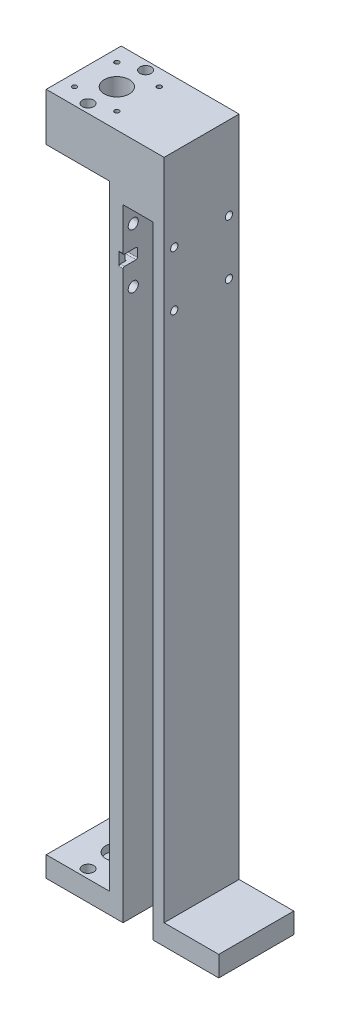
SolidWorks part; units mm, degrees
ref_plane "Front Plane" through (0, 0, 0) normal (0, 0, 1) x (1, 0, 0)
ref_plane "Top Plane" through (0, 0, 0) normal (0, 1, 0) x (1, 0, 0)
ref_plane "Right Plane" through (0, 0, 0) normal (1, 0, 0) x (0, 0, -1)
sketch "Sketch1" plane through (0, 0, 0) normal (0, 1, 0) x (1, 0, 0)
  line L5 (-28.12, -27.45) -> (-28.12, 27.45)
  line L6 (-28.12, -27.45) -> (28.12, -27.45)
  line L12 (28.12, 27.45) -> (28.12, -27.45)
  line L13 (28.12, 27.45) -> (-28.12, 27.45)
  circle A2 centre (-3.905, 21.045) radius 4.15
  circle A3 centre (-3.905, -21.045) radius 4.15
  point P5 (0, 27.45)
  point P6 (0, -27.45)
  point P15 (-28.12, 0)
  point P16 (28.12, 0)
  dimension "D1" = 42.09
  dimension "D2" = 8.3
  dimension "D3" = 8.3
  dimension "D8" = 24.215
  dimension "D4" = 6.405
  dimension "D5" = 56.24
  dimension "D6" = 54.9
  dimension "D7" = 6.405
extrude "Boss-Extrude1" add sketch "Sketch1" along normal blind 500 contours L13 L5 L6 A3 A2 region at (0.1418, 0, 0)
sketch "Sketch3" plane through (-28.12, 0, 0) normal (-1, 0, 0) x (0, 0, 1)
  line L2 (-27.45, 500) -> (-27.45, 0) construction
  line L9 (27.45, 500) -> (27.45, 0) construction
  line L11 (27.45, 465) -> (-27.45, 465)
  line L12 (27.45, 465) -> (27.45, 15)
  line L13 (27.45, 15) -> (-27.45, 15)
  line L14 (-27.45, 465) -> (-27.45, 15)
  point P0 (0, 15)
  point P2 (0, 465)
  dimension "D1" = 450
  dimension "D2" = 15
extrude "Cut-Extrude1" cut sketch "Sketch3" against normal blind 46.24
sketch "Sketch6" plane through (0, 500, 0) normal (0, 1, 0) x (1, 0, 0)
  line L0 (-3.905, 21.045) -> (-3.905, -21.045) construction
  line L1 (-28.12, -27.45) -> (-28.12, 27.45) construction
  line L3 (28.12, 27.45) -> (-28.12, 27.45) construction
  circle A0 centre (-3.905, 0) radius 9.15
  circle A1 centre (-19.405, 15.5) radius 1.65
  circle A2 centre (11.595, 15.5) radius 1.65
  circle A3 centre (11.595, -15.5) radius 1.65
  circle A4 centre (-19.405, -15.5) radius 1.65
  point P4 (-3.905, 0)
  dimension "D1" = 3.3
  dimension "D3" = 31
  dimension "D4" = 8.715
  dimension "D5" = 18.3
  dimension "D6" = 11.95
  dimension "D9" = 31
extrude "Cut-Extrude2" cut sketch "Sketch6" against normal blind 46.24
sketch "Sketch8" plane through (0, 15, 0) normal (0, 1, 0) x (1, 0, 0)
  circle A0 centre (-3.905, 0) radius 8.15
  circle A1 centre (-3.905, 0) radius 4.15
  dimension "D1" = 16.3
  dimension "D2" = 8.3
extrude "Cut-Extrude4" cut sketch "Sketch8" against normal blind 40 contours A1 region at (-3.905, 15, 0)
extrude "Cut-Extrude5" cut sketch "Sketch8<6>" against normal blind 5.2
sketch "Sketch8<6>" plane through (0, 15, 0) normal (0, 1, 0) x (1, 0, 0) same geometry as "Sketch8"
sketch "Sketch10" plane through (28.12, 0, 0) normal (1, 0, 0) x (0, 0, -1)
  line L0 (-27.45, 500) -> (-27.45, 0) construction
  line L1 (27.45, 500) -> (-27.45, 500)
  line L2 (27.45, 500) -> (27.45, 455)
  line L3 (27.45, 455) -> (-27.45, 455)
  line L4 (-27.45, 500) -> (-27.45, 455)
  dimension "D1" = 45
extrude "Boss-Extrude2" add sketch "Sketch10" along normal blind 22
sketch "Sketch11" plane through (0, 500, 0) normal (0, 1, 0) x (1, 0, 0)
  line L1 (50.12, 27.45) -> (58.12, 27.45)
  line L2 (50.12, 27.45) -> (50.12, -27.45)
  line L3 (50.12, -27.45) -> (58.12, -27.45)
  line L4 (58.12, 27.45) -> (58.12, -27.45)
  dimension "D1" = 8
  dimension "D2" = 54.9
extrude "Boss-Extrude3" add sketch "Sketch11" against normal blind 500
sketch "Sketch12" plane through (18.12, 0, 0) normal (-1, 0, 0) x (0, 0, 1)
  line L0 (-27.45, 465) -> (-27.45, 15) construction
  line L1 (27.45, 465) -> (-27.45, 465) construction
  circle A0 centre (-20, 439.3) radius 3.7
  circle A1 centre (-20, 439.3) radius 6
  circle A2 centre (20, 439.3) radius 6
  circle A3 centre (20, 439.3) radius 3.7
  circle A4 centre (20, 399.3) radius 6
  circle A5 centre (20, 399.3) radius 3.7
  circle A6 centre (-20, 399.3) radius 6
  circle A7 centre (-20, 399.3) radius 3.7
  dimension "D3" = 7.4
  dimension "D4" = 12
  dimension "D5" = 2
  dimension "D1" = 7.45
  dimension "D2" = 25.7
  dimension "D7" = 40
  dimension "D8" = 40
  dimension "D6" = 2
extrude "Cut-Extrude7" cut sketch "Sketch12" against normal blind 20 contours A7 | A0 | A5 | A3 region at (18.12, 439.3, -20) region at (18.12, 439.3, 20) region at (18.12, 399.3, 20) region at (18.12, 399.3, -20)
extrude "Cut-Extrude8" cut sketch "Sketch12<4>" against normal blind 4.8
sketch "Sketch12<4>" plane through (18.12, 0, 0) normal (-1, 0, 0) x (0, 0, 1) same geometry as "Sketch12"
sketch "Sketch13" plane through (58.12, 0, 0) normal (1, 0, 0) x (0, 0, -1)
  line L0 (27.45, 0) -> (27.45, 500) construction
  line L1 (-27.45, 0) -> (27.45, 0)
  line L2 (-27.45, 0) -> (-27.45, 15)
  line L3 (-27.45, 15) -> (27.45, 15)
  line L4 (27.45, 0) -> (27.45, 15)
  dimension "D1" = 15
extrude "Boss-Extrude4" add sketch "Sketch13" along normal blind 40
sketch "Sketch14" plane through (0, 465, 0) normal (0, -1, 0) x (1, 0, 0)
  circle A0 centre (-19.405, 15.5) radius 5
  circle A1 centre (11.595, 15.5) radius 5
  circle A2 centre (11.595, -15.5269) radius 5
  circle A3 centre (-19.405, -15.5269) radius 5
  dimension "D1" = 10
  dimension "D4" = 31
  dimension "D5" = 31.0269
  dimension "D2" = 2
  dimension "D3" = 2
extrude "Cut-Extrude9" cut sketch "Sketch14" against normal blind 25
sketch "Sketch15" plane through (50.12, 0, 0) normal (-1, 0, 0) x (0, 0, 1)
  circle A0 centre (-20, 439.3) radius 2.65
  circle A1 centre (20, 439.3) radius 2.65
  circle A2 centre (20, 399.3) radius 2.65
  circle A3 centre (-20, 399.3) radius 2.65
  dimension "D1" = 5.3
  dimension "D4" = 40
  dimension "D5" = 40
  dimension "D2" = 2
  dimension "D3" = 2
extrude "Cut-Extrude10" cut sketch "Sketch15" against normal blind 24.5
sketch "Sketch16" plane through (18.12, 0, 0) normal (-1, 0, 0) x (0, 0, 1)
  line L0 (-20, 439.3) -> (20, 439.3)
  line L1 (0, 439.3) -> (0, 396.651) construction
  line L2 (23, 416.4) -> (23, 422.2)
  line L7 (-22, 415.4) -> (-18, 415.4)
  line L8 (-23, 416.4) -> (-23, 422.2)
  line L9 (-22, 423.2) -> (-18, 423.2)
  line L10 (-17, 416.4) -> (-17, 422.2)
  line L11 (22, 415.4) -> (18, 415.4)
  line L12 (17, 416.4) -> (17, 422.2)
  line L13 (22, 423.2) -> (18, 423.2)
  arc A0 (-18, 415.4) -> (-17, 416.4) centre (-18, 416.4) ccw
  arc A1 (-22, 415.4) -> (-23, 416.4) centre (-22, 416.4) cw
  arc A2 (-17, 422.2) -> (-18, 423.2) centre (-18, 422.2) ccw
  arc A3 (-22, 423.2) -> (-23, 422.2) centre (-22, 422.2) ccw
  circle A4 centre (-20, 399.3) radius 6 construction
  arc A5 (22, 423.2) -> (23, 422.2) centre (22, 422.2) cw
  arc A6 (22, 415.4) -> (23, 416.4) centre (22, 416.4) ccw
  circle A7 centre (-20, 439.3) radius 6 construction
  arc A8 (18, 415.4) -> (17, 416.4) centre (18, 416.4) cw
  arc A9 (17, 422.2) -> (18, 423.2) centre (18, 422.2) cw
  point P36 (-20, 423.2)
  dimension "D1" = 1
  dimension "D3" = 5.8
  dimension "D2" = 16.1
  dimension "D4" = 4
  dimension "D5" = 16.1
extrude "Cut-Extrude11" cut sketch "Sketch16" against normal blind 15 contours L9 A3 L8 A1 L7 A0 L10 A2 | A9 L12 A8 L11 A6 L2 A5 L13 region at (18.12, 419.3, 20) region at (18.12, 419.3, -20)
sketch "Sketch18" plane through (28.12, 0, 0) normal (1, 0, 0) x (0, 0, -1)
  line L0 (26.45, 423.2) -> (22, 423.2)
  line L1 (27.45, 455) -> (27.45, 0) construction
  line L3 (22, 415.4) -> (26.45, 415.4)
  line L4 (27.45, 424.2) -> (27.45, 414.4)
  line L6 (22, 415.4) -> (22, 423.2)
  line L8 (-27.45, 424.2) -> (-27.45, 414.4)
  line L9 (-22, 415.4) -> (-26.45, 415.4)
  line L10 (-22, 415.4) -> (-22, 423.2)
  line L11 (-26.45, 423.2) -> (-22, 423.2)
  arc A0 (-26.45, 423.2) -> (-27.45, 424.2) centre (-26.45, 424.2) cw
  arc A1 (-27.45, 414.4) -> (-26.45, 415.4) centre (-26.45, 414.4) cw
  arc A2 (27.45, 414.4) -> (26.45, 415.4) centre (26.45, 414.4) ccw
  arc A3 (26.45, 423.2) -> (27.45, 424.2) centre (26.45, 424.2) ccw
  point P1 (0, 0)
  point P5 (0, 0)
  point P9 (0, 0)
  point P10 (26.45, 415.4)
  point P15 (27.45, 415.4)
  point P19 (27.45, 423.2)
  point P20 (27.45, 414.4)
  point P25 (22, 423.2)
  point P28 (0, 0)
  point P29 (0, 0)
  point P30 (0, 0)
  point P31 (0, 0)
  point P32 (0, 0)
  dimension "D1" = 9.8
  dimension "D2" = 1
  dimension "D7" = 1
  dimension "D3" = 5.45
  dimension "D4" = 5.45
  dimension "D5" = 44
  dimension "D6" = 9.8
  dimension "D9" = 7.8
  dimension "D10" = 4.45
  dimension "D11" = 4.45
extrude "Cut-Extrude14" cut sketch "Sketch18" against normal blind 3
